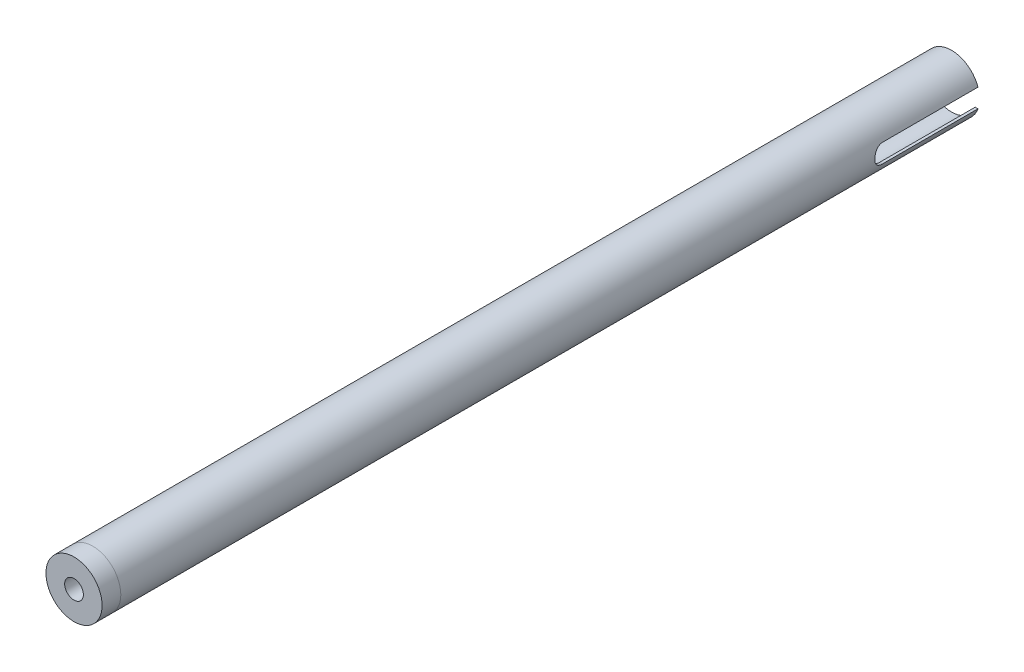
SolidWorks part; units mm, degrees
material "AISI 4130 Steel, normalized at 870C"
ref_plane "Front Plane" through (0, 0, 0) normal (0, 0, 1) x (1, 0, 0)
ref_plane "Top Plane" through (0, 0, 0) normal (0, 1, 0) x (1, 0, 0)
ref_plane "Right Plane" through (0, 0, 0) normal (1, 0, 0) x (0, 0, -1)
sketch "Axis" plane through (0, 0, 0) normal (0, 1, 0) x (1, 0, 0)
  line L0 (0, 0) -> (0, 297.7329) construction
  line L1 (0, 0) -> (0, -28.575) construction
  line L2 (0, 297.7329) -> (-9.525, 297.7329) construction
  line L3 (0, 325.6748) -> (-22.1529, 260.6883) construction
  dimension "D1" = 28.575
  dimension "D2" = 9.525
sketch "Sketch1" plane through (0, 0, 0) normal (0, 0, 1) x (1, 0, 0)
  line L0 (-9.525, 0) -> (9.525, 0) construction
  line L1 (-8.9803, 3.175) -> (8.9803, 3.175)
  line L2 (-8.9803, -3.175) -> (8.9803, -3.175)
  circle A0 centre (0, 0) radius 9.525
  circle A1 centre (0, 0) radius 8.636
  circle A2 centre (0, 0) radius 3.175
  dimension "D1" = 19.05
  dimension "D3" = 6.35
  dimension "D2" = 0.889
  dimension "D4" = 6.35
extrude "Threaded insert 1-1" add sketch "Sketch1" against normal blind 6.35 contours A2 L1 A1 | A1 L1 A0 | A2 L0 A1 L1 | A1 L0 A0 L1 | L0 A1 L2 A0 | L0 A2 L2 A1 | A2 L2 A1 | A1 L2 A0 | L0 A1 L2 A2 | L0 A0 L2 A1 | A0 L0 A1 L1 | A1 L0 A2 L1 region at (5.4259, 1.6615, 0) region at (5.4259, -1.6615, 0) region at (8.8881, 1.6046, 0) region at (8.8881, -1.6046, 0) region at (-5.4259, -1.6615, 0) region at (-5.4259, 1.6615, 0) region at (0, 5.4321, 0) region at (0, -5.4321, 0) region at (0, 8.8265, 0) region at (8.5057, -3.3655, 0) region at (-8.8881, -1.6046, 0) region at (-8.8881, 1.6046, 0)
extrude "Threaded insert 1-2" add sketch "Sketch1<3>" against normal blind 9.525 from surface contours A2 L1 A1 | A2 L0 A1 L1 | L0 A2 L2 A1 | A2 L2 A1 | L0 A1 L2 A2 | A1 L0 A2 L1 region at (5.4259, 1.6615, 0) region at (5.4259, -1.6615, 0) region at (-5.4259, -1.6615, 0) region at (-5.4259, 1.6615, 0) region at (0, 5.4321, 0) region at (0, -5.4321, 0) starting at face at (9.525, 0, -6.35)
sketch "Sketch1<3>" plane through (0, 0, 0) normal (0, 0, 1) x (1, 0, 0) same geometry as "Sketch1"
extrude "A-arm tube" add sketch "Sketch1<4>" against normal up to vertex (297.7329 mm away) from surface separate body contours A1 L1 A0 | A1 L0 A0 L1 | L0 A1 L2 A0 | A1 L2 A0 | L0 A0 L2 A1 | A0 L0 A1 L1 region at (8.8881, 1.6046, 0) region at (8.8881, -1.6046, 0) region at (0, 8.8265, 0) region at (8.5057, -3.3655, 0) region at (-8.8881, -1.6046, 0) region at (-8.8881, 1.6046, 0) up to point (0, 0, -297.7329) starting at face at (8.636, 0, -6.35)
sketch "Sketch1<4>" plane through (0, 0, 0) normal (0, 0, 1) x (1, 0, 0) same geometry as "Sketch1"
extrude "Apex slot" cut sketch "Sketch1<5>" along normal blind 35.56 from surface contours A0 L0 A1 L1 | L0 A0 L2 A1 | A1 L0 A0 L1 | L0 A1 L2 A0 region at (8.8881, 1.6046, 0) region at (8.8881, -1.6046, 0) region at (-8.8881, -1.6046, 0) region at (-8.8881, 1.6046, 0) starting at face at (8.636, 0, -297.7329)
sketch "Sketch1<5>" plane through (0, 0, 0) normal (0, 0, 1) x (1, 0, 0) same geometry as "Sketch1"
fillet "Fillet1" radius 3.175 4 edges at (-8.5057, 3.175, -262.1729) (-8.5057, -3.175, -262.1729) (8.5057, -3.175, -262.1729) (8.5057, 3.175, -262.1729)
equation "\"tube diameter\"= 3 / 4"
equation "\"tube thickness\"= .035"
equation "\"apex thickness\"= .25"
equation "\"tube slot\"= 1.4"
equation "\"D1@Sketch1\"=\"tube diameter\""
equation "\"D2@Sketch1\"=\"tube thickness\""
equation "\"threaded insert hole\"= 1 / 4"
equation "\"D3@Sketch1\"=\"threaded insert hole\""
equation "\"D4@Sketch1\"=\"apex thickness\""
equation "\"D1@Apex slot\" = \"tube slot\""
equation "\"D1@Fillet1\"=\"apex thickness\"/2"
equation "\"D2@Axis\"=\"tube diameter\"/2"
